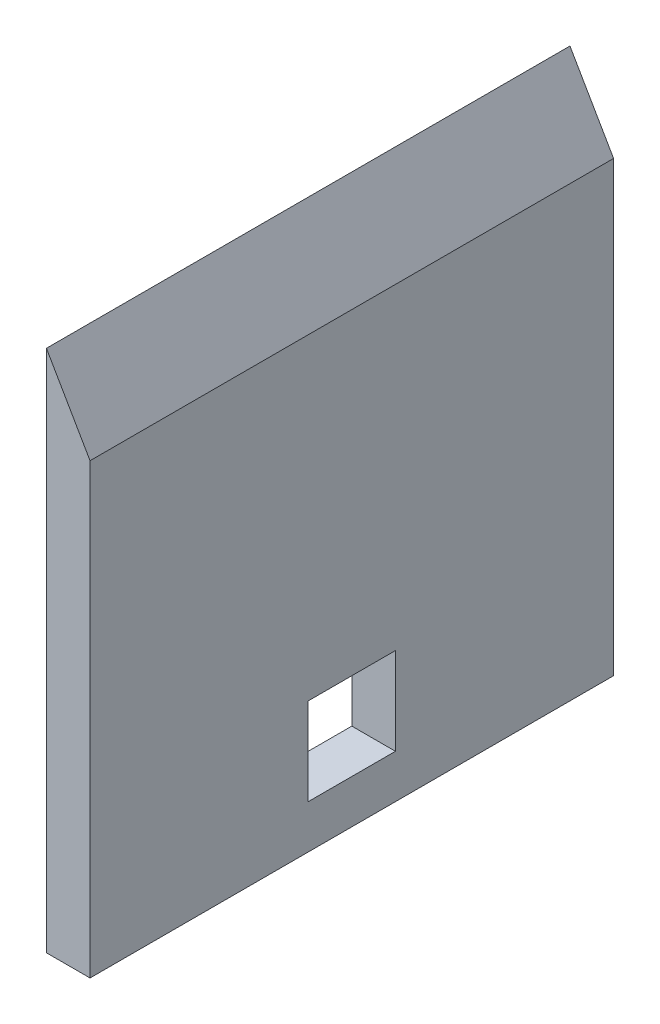
SolidWorks part; units mm, degrees
material "Pino"
ref_plane "Alzado" through (0, 0, 0) normal (0, 0, 1) x (1, 0, 0)
ref_plane "Planta" through (0, 0, 0) normal (0, 1, 0) x (1, 0, 0)
ref_plane "Vista lateral" through (0, 0, 0) normal (1, 0, 0) x (0, 0, -1)
sketch "Croquis1" plane through (0, 0, 0) normal (1, 0, 0) x (0, 0, -1)
  line L1 (-152.4, 0) -> (152.4, 0)
  line L2 (-152.4, 0) -> (-152.4, 304.8)
  line L3 (-152.4, 304.8) -> (152.4, 304.8)
  line L4 (152.4, 0) -> (152.4, 304.8)
  point P4 (0, 0)
  dimension "D1" = 304.8
  dimension "D2" = 304.8
extrude "Saliente-Extruir1" add sketch "Croquis1" against normal blind 25.4
sketch "Croquis2" plane through (0, 0, 152.4) normal (0, 0, 1) x (1, 0, 0)
  line L0 (-25.4, 304.8) -> (0, 260.8059)
  line L1 (0, 304.8) -> (0, 0) construction
  line L2 (0, 260.8059) -> (0, 304.8)
  line L3 (0, 304.8) -> (-25.4, 304.8)
  dimension "D1" = 60
extrude "Cortar-Extruir1" cut sketch "Croquis2" against normal up to surface (304.8 mm away) up to face at (-12.7, 152.4, -152.4)
sketch "Croquis3" plane through (0, 0, 0) normal (1, 0, 0) x (0, 0, -1)
  line L0 (-152.4, 0) -> (152.4, 0) construction
  line L1 (-25.4, 25.4) -> (25.4, 25.4)
  line L2 (-25.4, 25.4) -> (-25.4, 76.2)
  line L3 (-25.4, 76.2) -> (25.4, 76.2)
  line L4 (25.4, 25.4) -> (25.4, 76.2)
  line L5 (-25.4, 25.4) -> (25.4, 76.2) construction
  line L6 (-25.4, 76.2) -> (25.4, 25.4) construction
  point P0 (0, 50.8)
  dimension "D1" = 50.8
  dimension "D2" = 50.8
  dimension "D3" = 25.4
extrude "Cortar-Extruir2" cut sketch "Croquis3" against normal up to surface (25.4 mm away) up to face at (-25.4, 152.4, 0)
